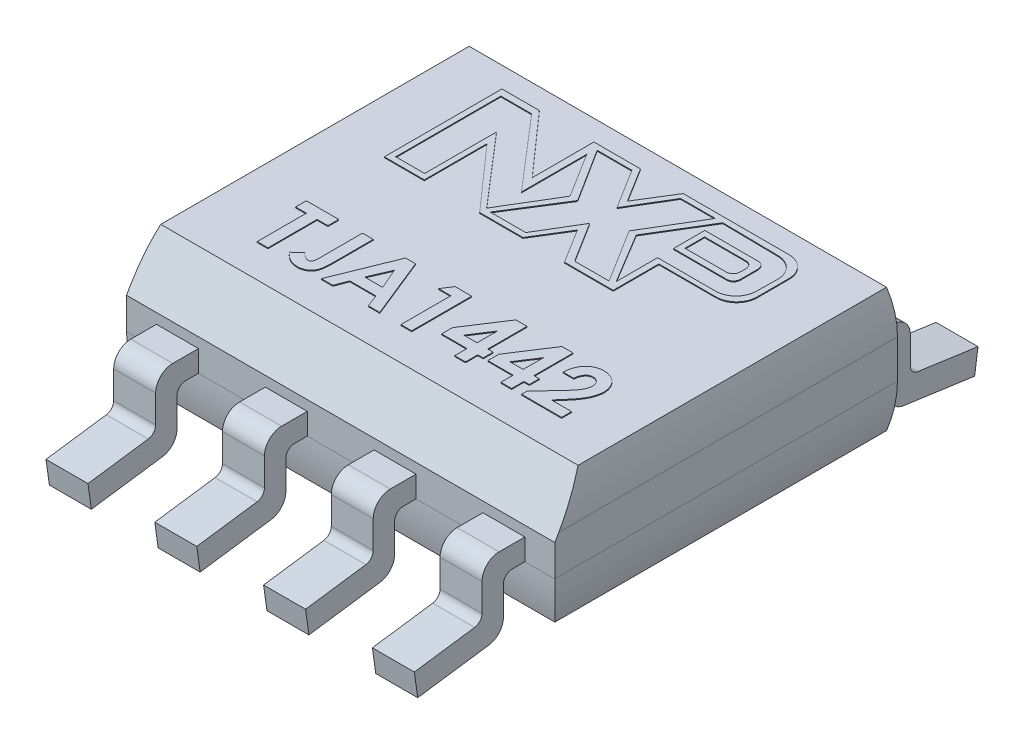
SolidWorks part; units mm, degrees
ref_plane "Front Plane" through (0, 0, 0) normal (0, 0, 1) x (1, 0, 0)
ref_plane "Top Plane" through (0, 0, 0) normal (0, 1, 0) x (1, 0, 0)
ref_plane "Right Plane" through (0, 0, 0) normal (1, 0, 0) x (0, 0, -1)
sketch "Sketch1" plane through (0, 0, 0) normal (0, 1, 0) x (1, 0, 0)
  line L1 (-2.5, 2) -> (2.5, 2)
  line L2 (-2.5, 2) -> (-2.5, -2)
  line L3 (-2.5, -2) -> (2.5, -2)
  line L4 (2.5, 2) -> (2.5, -2)
  line L5 (-2.5, 2) -> (2.5, -2) construction
  line L6 (-2.5, -2) -> (2.5, 2) construction
  point P0 (0, 0)
  dimension "D1" = 5
  dimension "D2" = 4
extrude "Boss-Extrude1" add sketch "Sketch1" along normal blind 1.45
sketch "Sketch2" plane through (-2.5, 0, 0) normal (-1, 0, 0) x (0, 0, 1)
  line L0 (2, 0.8687) -> (1.6644, 1.45)
  line L1 (2, 1.45) -> (2, 0) construction
  line L2 (-2, 1.45) -> (2, 1.45) construction
  line L3 (0, 0) -> (0, 0.828) construction
  line L4 (-2, 0.725) -> (-1.3983, 0.725) construction
  line L6 (-2, 1.45) -> (-2, 0) construction
  line L7 (-1.8644, 1.6723) -> (-2.1559, 1.6723)
  line L8 (-2.1559, 1.6723) -> (-2.1559, 0.954)
  line L9 (-2.1559, 0.954) -> (-2, 0.9484)
  line L10 (-2, 0.5016) -> (-2.1559, 0.5016)
  line L11 (-2.1559, 0.5016) -> (-2.1559, -0.2223)
  line L12 (-2.1559, -0.2223) -> (-1.8644, -0.2223)
  line L13 (1.6644, 1.45) -> (1.6644, 1.7317)
  line L14 (1.6644, 1.7317) -> (2.4871, 1.7317)
  line L15 (2.4871, 1.7317) -> (2.4871, 0.8687)
  line L16 (2.4871, 0.8687) -> (2, 0.8687)
  line L17 (2, 0.5015) -> (2.4871, 0.5015)
  line L18 (2.4871, 0.5015) -> (2.4871, -0.2223)
  line L19 (2.4871, -0.2223) -> (1.8644, -0.2223)
  arc A0 (2, 0.5015) -> (1.8644, -0.2223) centre (0, 0.5015) cw
  arc A1 (-2, 0.5016) -> (-1.8644, -0.2223) centre (0, 0.5015) ccw
  arc A2 (-2, 0.9484) -> (-1.8644, 1.6723) centre (0, 0.9485) cw
  dimension "D1" = 2
  dimension "D2" = 60
extrude "Cut-Extrude1" cut sketch "Sketch2" against normal blind 61.45
sketch "Sketch5" plane through (0, 0, -2) normal (0, 0, -1) x (-1, 0, 0)
  line L1 (0, 1.45) -> (0, 1.0867) construction
  line L2 (-3.4587, 0.725) -> (-2.857, 0.725) construction
  line L3 (-2.3644, 1.6723) -> (-2.6559, 1.6723)
  line L4 (-2.6559, 1.6723) -> (-2.6559, 0.954)
  line L5 (-2.6559, 0.954) -> (-2.5, 0.9484)
  line L6 (-2.5, 0.5016) -> (-2.6559, 0.5016)
  line L7 (-2.6559, 0.5016) -> (-2.6559, -0.2223)
  line L8 (-2.6559, -0.2223) -> (-2.3644, -0.2223)
  line L16 (2.5, 1.45) -> (-2.5, 1.45) construction
  line L17 (-2.6559, 1.6723) -> (-2.3644, 1.6723)
  line L18 (-2.6559, 0.9484) -> (-2.6559, 1.6723)
  line L19 (-2.5, 0.9484) -> (-2.6559, 0.9484)
  line L20 (-2.6559, 0.496) -> (-2.5, 0.5016)
  line L21 (-2.6559, -0.2223) -> (-2.6559, 0.496)
  line L22 (-2.3644, -0.2223) -> (-2.6559, -0.2223)
  line L23 (2.6559, -0.2223) -> (2.3644, -0.2223)
  line L24 (2.6559, 0.5016) -> (2.6559, -0.2223)
  line L25 (2.5, 0.5016) -> (2.6559, 0.5016)
  line L26 (2.6559, 0.954) -> (2.5, 0.9484)
  line L27 (2.6559, 1.6723) -> (2.6559, 0.954)
  line L28 (2.3644, 1.6723) -> (2.6559, 1.6723)
  arc A1 (-2.5, 0.5016) -> (-2.3644, -0.2223) centre (-0.5, 0.5015) ccw
  arc A2 (-2.5, 0.9484) -> (-2.3644, 1.6723) centre (-0.5, 0.9485) cw
  arc A3 (-2.5, 0.5016) -> (-2.3644, -0.2223) centre (-0.5, 0.5015) ccw
  arc A4 (-2.5, 0.9484) -> (-2.3644, 1.6723) centre (-0.5, 0.9485) cw
  arc A5 (2.5, 0.5016) -> (2.3644, -0.2223) centre (0.5, 0.5015) cw
  arc A6 (2.5, 0.9484) -> (2.3644, 1.6723) centre (0.5, 0.9485) ccw
extrude "Cut-Extrude2" cut sketch "Sketch5" against normal blind 61.45 contours L5 A2 L3 L4 | A1 L20 L7 L22 | A6 L26 L27 L28 | L25 A5 L23 L24
sketch "Sketch6" plane through (-2.5, 0, 0) normal (-1, 0, 0) x (0, 0, 1)
  line L5 (1.9361, 0) -> (-1.9361, 0) construction
  line L7 (0, 0) -> (0, -0.7239) construction
  line L8 (2.2535, 0.75) -> (2.3, 0.75)
  line L9 (2.5, 0.55) -> (2.5, 0.2276)
  line L10 (2.5, 0.1406) -> (3.25, 0.1406) construction
  line L11 (3.25, 0.1406) -> (3.25, -0.1094) construction
  line L12 (3.25, -0.1094) -> (2.25, -0.1094) construction
  line L13 (2.25, 0.0645) -> (2.25, 0.4)
  line L14 (2.25, 0.5) -> (2.2535, 0.5)
  line L15 (-3.25, -0.1094) -> (-2.25, -0.1094) construction
  line L17 (2.4222, -0.1335) -> (3.2508, -0.25)
  line L18 (2.5861, 0.1286) -> (3.2901, 0.0296)
  line L19 (3.2508, -0.25) -> (3.2901, 0.0296)
  line L20 (-3.25, 0.1406) -> (-3.25, -0.1094) construction
  line L21 (-2.5, 0.1406) -> (-3.25, 0.1406) construction
  line L22 (-3.2508, -0.25) -> (-3.2901, 0.0296)
  line L23 (-2.5861, 0.1286) -> (-3.2901, 0.0296)
  line L24 (-2.4222, -0.1335) -> (-3.2508, -0.25)
  line L25 (-2.25, 0.5) -> (-2.2535, 0.5)
  line L26 (-2.25, 0.0645) -> (-2.25, 0.4)
  line L27 (-2.5, 0.55) -> (-2.5, 0.2276)
  line L28 (-2.2535, 0.75) -> (-2.3, 0.75)
  line L29 (-2.15, 0.5) -> (2.15, 0.5)
  line L30 (-2.2535, 0.75) -> (2.2535, 0.75)
  arc A0 (2.4222, -0.1335) -> (2.25, 0.0645) centre (2.45, 0.0645) cw
  arc A1 (2.5, 0.55) -> (2.3, 0.75) centre (2.3, 0.55) ccw
  arc A2 (2.5861, 0.1286) -> (2.5, 0.2276) centre (2.6, 0.2276) cw
  arc A3 (2.25, 0.4) -> (2.15, 0.5) centre (2.15, 0.4) ccw
  arc A4 (-2.25, 0.4) -> (-2.15, 0.5) centre (-2.15, 0.4) cw
  arc A5 (-2.5861, 0.1286) -> (-2.5, 0.2276) centre (-2.6, 0.2276) ccw
  arc A6 (-2.5, 0.55) -> (-2.3, 0.75) centre (-2.3, 0.55) cw
  arc A7 (-2.4222, -0.1335) -> (-2.25, 0.0645) centre (-2.45, 0.0645) ccw
  dimension "D9" = 0.2
  dimension "D10" = 0.1
  dimension "D4" = 0.25
  dimension "D5" = 0.25
  dimension "D6" = 1
  dimension "D7" = 8
  dimension "D8" = 0.25
extrude "Boss-Extrude2" add sketch "Sketch6" against normal up to surface (5 mm away) up to face at (2.5, 0.8431, 0.3908)
sketch "Sketch7" plane through (0, 1.45, 0) normal (0, 1, 0) x (1, 0, 0)
  line L0 (2.5, -2) -> (-2.5, -2) construction
  line L1 (-2.5, -2) -> (-2.15, -2)
  line L2 (-2.5, -2) -> (-2.5, -3.534)
  line L3 (-2.5, -3.534) -> (-2.15, -3.534)
  line L4 (-2.15, -2) -> (-2.15, -3.534)
  line L5 (-1.66, -2) -> (-0.88, -2)
  line L6 (-1.66, -2) -> (-1.66, -3.6106)
  line L7 (-1.66, -3.6106) -> (-0.88, -3.6106)
  line L8 (-0.88, -2) -> (-0.88, -3.6106)
  line L9 (0, 0) -> (-3.4858, 0) construction
  line L10 (-0.39, -2) -> (0.39, -2)
  line L11 (-0.39, -2) -> (-0.39, -3.6106)
  line L12 (-0.39, -3.6106) -> (0.39, -3.6106)
  line L13 (0.39, -2) -> (0.39, -3.6106)
  line L14 (2.5, -2) -> (2.15, -2)
  line L15 (2.5, -2) -> (2.5, -3.783)
  line L16 (2.5, -3.783) -> (2.15, -3.783)
  line L17 (2.15, -2) -> (2.15, -3.783)
  line L18 (1.66, -2) -> (0.88, -2)
  line L19 (1.66, -2) -> (1.66, -3.6776)
  line L20 (1.66, -3.6776) -> (0.88, -3.6776)
  line L21 (0.88, -2) -> (0.88, -3.6776)
  line L22 (0.88, 2) -> (0.88, 3.6776)
  line L23 (1.66, 3.6776) -> (0.88, 3.6776)
  line L24 (1.66, 2) -> (1.66, 3.6776)
  line L25 (1.66, 2) -> (0.88, 2)
  line L26 (2.15, 2) -> (2.15, 3.783)
  line L27 (2.5, 3.783) -> (2.15, 3.783)
  line L28 (2.5, 2) -> (2.5, 3.783)
  line L29 (2.5, 2) -> (2.15, 2)
  line L30 (0.39, 2) -> (0.39, 3.6106)
  line L31 (-0.39, 3.6106) -> (0.39, 3.6106)
  line L32 (-0.39, 2) -> (-0.39, 3.6106)
  line L33 (-0.39, 2) -> (0.39, 2)
  line L34 (-0.88, 2) -> (-0.88, 3.6106)
  line L35 (-1.66, 3.6106) -> (-0.88, 3.6106)
  line L36 (-1.66, 2) -> (-1.66, 3.6106)
  line L37 (-1.66, 2) -> (-0.88, 2)
  line L38 (-2.15, 2) -> (-2.15, 3.534)
  line L39 (-2.5, 3.534) -> (-2.15, 3.534)
  line L40 (-2.5, 2) -> (-2.5, 3.534)
  line L41 (-2.5, 2) -> (-2.15, 2)
  dimension "D1" = 0.49
  dimension "D2" = 0.49
  dimension "D3" = 0.49
  dimension "D4" = 0.49
  dimension "D5" = 0.78
  dimension "D6" = 0.78
  dimension "D7" = 0.78
  dimension "D8" = 0.35
extrude "Cut-Extrude3" cut sketch "Sketch7" against normal blind 61.45
sketch "Sketch8" plane through (0, 1.45, 0) normal (0, 1, 0) x (1, 0, 0)
  line L0 (70.6653, 255.7964) -> (518.6653, 255.7964) construction
  line L1 (-1.8034, 0.3139) -> (-1.8034, 1.6861)
  line L2 (-1.8034, 1.6861) -> (-1.3672, 1.6861)
  line L3 (-1.3672, 1.6861) -> (-0.7295, 0.965)
  line L4 (-0.7295, 0.965) -> (-0.7295, 1.6861)
  line L5 (-0.7295, 1.6861) -> (-0.186, 1.6861)
  line L6 (-0.186, 1.6861) -> (0.0636, 1.2836)
  line L7 (0.0636, 1.2836) -> (0.3123, 1.6861)
  line L8 (0.3123, 1.6861) -> (1.5487, 1.6861)
  line L9 (1.7887, 1.4461) -> (1.7887, 1.0732)
  line L10 (1.5487, 0.8332) -> (0.8817, 0.8332)
  line L11 (0.8817, 0.8332) -> (0.8817, 0.2999)
  line L12 (0.8817, 0.2999) -> (0.3123, 0.2999)
  line L13 (0.3123, 0.2999) -> (0.0636, 0.7007)
  line L14 (0.0636, 0.7007) -> (-0.1796, 0.3069)
  line L15 (-0.1796, 0.3069) -> (-0.6842, 0.3069)
  line L16 (-0.6842, 0.3069) -> (-1.3377, 1.046)
  line L17 (-1.3377, 1.046) -> (-1.3377, 0.3139)
  line L18 (-1.3377, 0.3139) -> (-1.8034, 0.3139)
  line L19 (-1.7377, 0.3801) -> (-1.7377, 1.6079)
  line L20 (-1.7377, 1.6079) -> (-1.3789, 1.6079)
  line L21 (-1.3789, 1.6079) -> (-0.6481, 0.759)
  line L22 (-0.6481, 0.759) -> (-0.6481, 1.5221)
  line L23 (-0.6481, 1.5221) -> (-0.3221, 0.9996)
  line L24 (-0.3221, 0.9996) -> (-0.6875, 0.3914)
  line L25 (-0.6875, 0.3914) -> (-1.3999, 1.219)
  line L26 (-1.3999, 1.219) -> (-1.3999, 0.3801)
  line L27 (-1.3999, 0.3801) -> (-1.7377, 0.3801)
  line L28 (-0.6279, 1.6222) -> (-0.2222, 1.6222)
  line L29 (-0.2222, 1.6222) -> (0.068, 1.1578)
  line L30 (0.068, 1.1578) -> (0.3464, 1.6222)
  line L31 (0.3464, 1.6222) -> (0.7514, 1.6222)
  line L32 (0.7514, 1.6222) -> (0.3743, 0.9932)
  line L33 (0.3743, 0.9932) -> (0.7643, 0.369)
  line L34 (0.7643, 0.369) -> (0.3619, 0.369)
  line L35 (0.3619, 0.369) -> (0.068, 0.8394)
  line L36 (0.068, 0.8394) -> (-0.2117, 0.373)
  line L37 (-0.2117, 0.373) -> (-0.6279, 0.373)
  line L38 (-0.6279, 0.373) -> (-0.2334, 0.9996)
  line L39 (-0.2334, 0.9996) -> (-0.6279, 1.6222)
  line L40 (0.8381, 1.6222) -> (1.4939, 1.613)
  line L41 (1.7305, 1.3696) -> (1.727, 1.1248)
  line L42 (1.4871, 0.8882) -> (0.8112, 0.8882)
  line L43 (0.8112, 0.8882) -> (0.8112, 0.4059)
  line L44 (0.8112, 0.4059) -> (0.4571, 0.9932)
  line L45 (0.4571, 0.9932) -> (0.8381, 1.6222)
  line L46 (0.8112, 1.4396) -> (1.433, 1.4396)
  line L47 (1.513, 1.3596) -> (1.513, 1.1532)
  line L48 (1.433, 1.0732) -> (0.8112, 1.0732)
  line L49 (0.8112, 1.4396) -> (0.8112, 1.0732)
  line L50 (0.8755, 1.3732) -> (1.3583, 1.3732)
  line L51 (0.8755, 1.3732) -> (0.8755, 1.144)
  line L52 (0.8755, 1.144) -> (1.3583, 1.144)
  line L53 (1.4383, 1.2932) -> (1.4383, 1.224)
  arc A0 (1.7887, 1.0732) -> (1.5487, 0.8332) centre (1.5487, 1.0732) cw
  arc A1 (1.5487, 1.6861) -> (1.7887, 1.4461) centre (1.5487, 1.4461) cw
  arc A2 (1.727, 1.1248) -> (1.4871, 0.8882) centre (1.4871, 1.1282) cw
  arc A3 (1.4939, 1.613) -> (1.7305, 1.3696) centre (1.4905, 1.373) cw
  arc A4 (1.3583, 1.144) -> (1.4383, 1.224) centre (1.3583, 1.224) ccw
  arc A5 (1.3583, 1.3732) -> (1.4383, 1.2932) centre (1.3583, 1.2932) cw
  arc A6 (1.513, 1.1532) -> (1.433, 1.0732) centre (1.433, 1.1532) cw
  arc A7 (1.433, 1.4396) -> (1.513, 1.3596) centre (1.433, 1.3596) cw
extrude "Boss-Extrude3" add sketch "Sketch8" along normal blind 0.01 contours A1 L8 L7 L6 L5 L4 L3 L2 L1 L18 L17 L16 L15 L14 L13 L12 L11 L10 A0 L9 L38 L39 L28 L29 L30 L31 L32 L33 L34 L35 L36 L37 L26 L27 L19 L20 L21 L22 L23 L24 L25 L40 A3 L41 A2 L42 L43 L44 | A7 L46 L49 L48 A6 L47 L50 A5 L53 A4 L52 L51
sketch "Sketch9" plane through (0, 1.45, 0) normal (0, 1, 0) x (1, 0, 0)
  line L0 (-1.8233, -1.2861) -> (2.2013, -1.2861) construction
  text T0 "<b>TJA1442</b>" font "Century Gothic" height 0.7
extrude "Boss-Extrude4" add sketch "Sketch9" along normal blind 0.01
